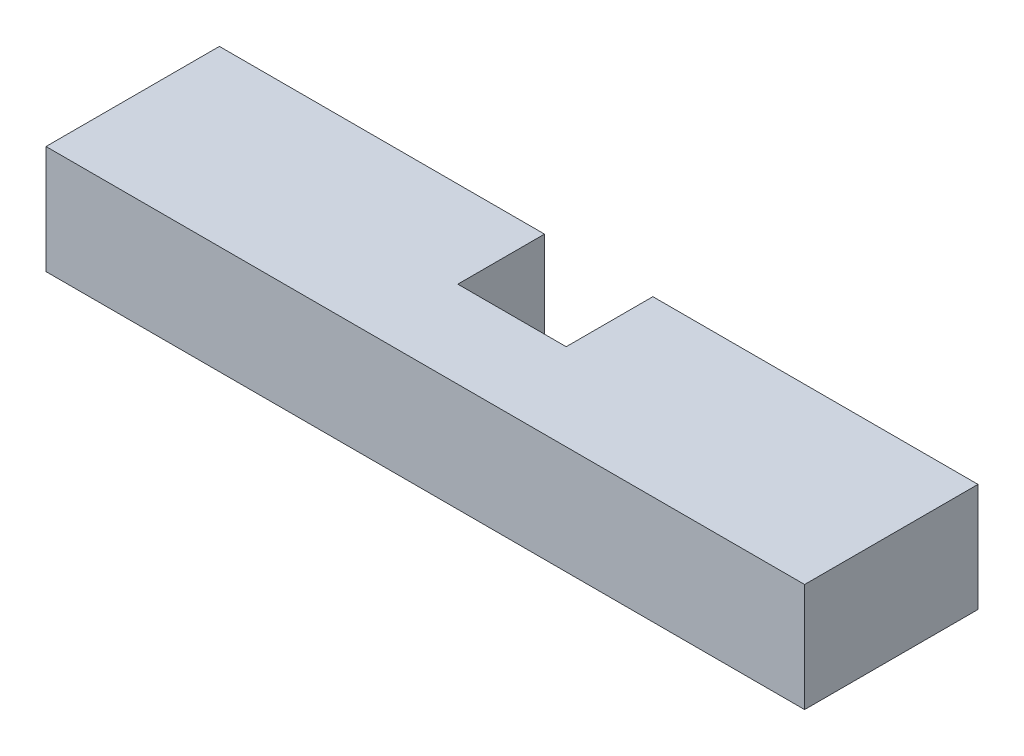
SolidWorks part; units mm, degrees
ref_plane "Front Plane" through (0, 0, 0) normal (0, 0, 1) x (1, 0, 0)
ref_plane "Top Plane" through (0, 0, 0) normal (0, 1, 0) x (1, 0, 0)
ref_plane "Right Plane" through (0, 0, 0) normal (1, 0, 0) x (0, 0, -1)
sketch "Elevator Paddle Support Strut" plane through (0, 0, 0) normal (0, 1, 0) x (1, 0, 0)
  line L0 (0, -5.08) -> (0, 0) construction
  line L1 (-22.225, -5.08) -> (22.225, -5.08)
  line L2 (-22.225, -5.08) -> (-22.225, 5.08)
  line L3 (-22.225, 5.08) -> (-3.175, 5.08)
  line L4 (22.225, -5.08) -> (22.225, 5.08)
  line L5 (-22.225, -5.08) -> (0, 0) construction
  line L6 (-22.225, 5.08) -> (-3.175, 0.7257) construction
  line L7 (-22.225, 0) -> (22.225, 0) construction
  line L8 (-3.175, 0) -> (3.175, 0)
  line L9 (-3.175, 0) -> (-3.175, 5.08)
  line L10 (3.175, 0.7257) -> (22.225, 5.08) construction
  line L11 (3.175, 0) -> (3.175, 5.08)
  line L13 (0, 0) -> (22.225, -5.08) construction
  line L14 (3.175, 5.08) -> (22.225, 5.08)
  point P0 (0, 0)
  point P8 (0, 0)
  dimension "D1" = 10.16
  dimension "D2" = 44.45
  dimension "D3" = 6.35
extrude "Boss-Extrude1" add sketch "Elevator Paddle Support Strut" along normal blind 6.35 contours L11 L8 L9 L3 L2 L1 L4 region at (0, 0, 0.1954)
equation "\"Ball Diameter\"= 1.75in"
equation "\"Sheet Thickness\"= 0.25in"
equation "\"Screw Diameter\"= .17in"
equation "\"Robot Diameter\"= 14in"
equation "\"Castor Screw Diameter\"= 0.22in"
equation "\"Wheel Diameter\" = 4in"
equation "\"Nut Diameter\" = 8.4mm"
equation "\"Nut Height\" = 2.9mm"
equation "\"Screw Height\" = 0.55in"
equation "\"D2@Elevator Paddle Support Strut\"=\"Ball Diameter\""
equation "\"D3@Elevator Paddle Support Strut\"=\"Sheet Thickness\""
equation "\"D1@Boss-Extrude1\"=\"Sheet Thickness\""
